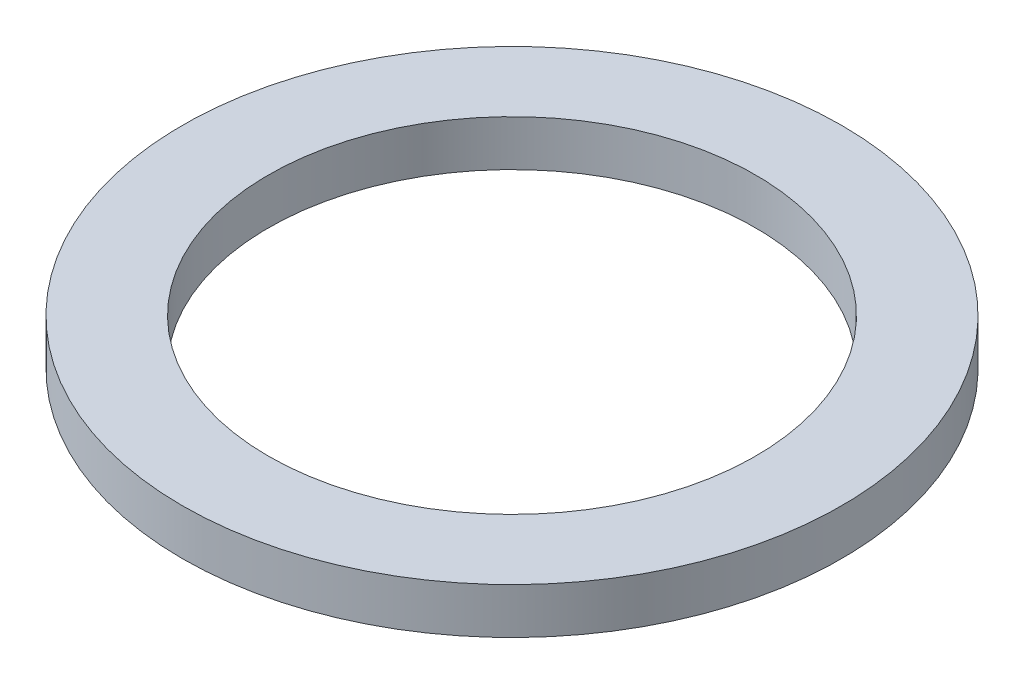
SolidWorks part; units mm, degrees
ref_plane "Front Plane" through (0, 0, 0) normal (0, 0, 1) x (1, 0, 0)
ref_plane "Top Plane" through (0, 0, 0) normal (0, 1, 0) x (1, 0, 0)
ref_plane "Right Plane" through (0, 0, 0) normal (1, 0, 0) x (0, 0, -1)
sketch "Sketch1" plane through (0, 0, 0) normal (0, 1, 0) x (1, 0, 0)
  circle A0 centre (0, 0) radius 57.5
  dimension "FLANGE_OD" = 115
extrude "Boss-Extrude1" add sketch "Sketch1" along normal blind 8
sketch "Sketch2" plane through (0, 0, 0) normal (0, 1, 0) x (1, 0, 0)
  circle A0 centre (0, 0) radius 42.5
  dimension "BORE_D" = 85
extrude "Cut-Extrude1" cut sketch "Sketch2" along normal through all
sketch "Sketch3" plane through (0, 8, 0) normal (0, 1, 0) x (1, 0, 0)
  circle A0 centre (0, 0) radius 24.8055 construction
  circle A1 centre (-24.8055, 0) radius 1.9673
  dimension "BOLT_D" = 3.9345
  dimension "BOLT_PCD" = 49.611
extrude "Cut-Extrude2" cut sketch "Sketch3" against normal blind 5.3907 rebuild error yes
pattern_circular "CirPattern1" count 5 over 360 rebuild error yes
